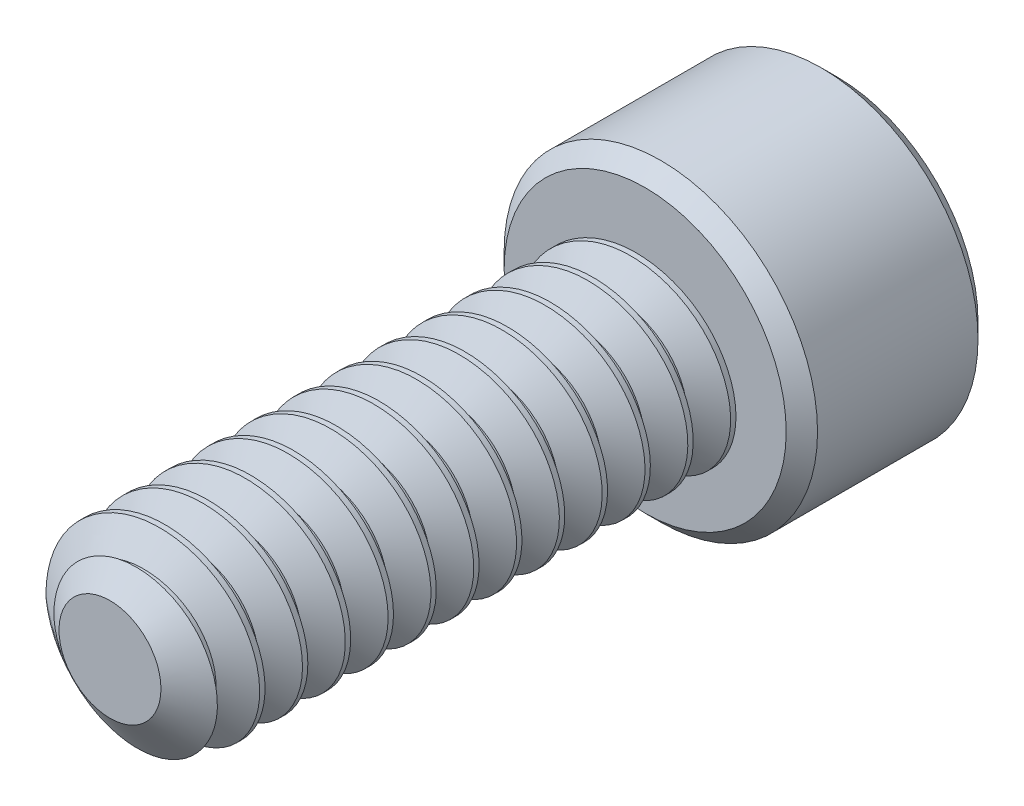
SolidWorks part; units mm, degrees
material "Alloy Steel"
ref_plane "Front Plane" through (0, 0, 0) normal (0, 0, 1) x (1, 0, 0)
ref_plane "Top Plane" through (0, 0, 0) normal (0, 1, 0) x (1, 0, 0)
ref_plane "Right Plane" through (0, 0, 0) normal (1, 0, 0) x (0, 0, -1)
sketch "Sketch1" plane through (0, 0, 0) normal (0, 0, 1) x (1, 0, 0)
  circle A0 centre (0, 0) radius 1.4224
  dimension "OD" = 2.8448
extrude "Extrude1" add sketch "Sketch1" against normal blind 7.9375
sketch "Sketch2" plane through (0, 0, 0) normal (0, 0, 1) x (1, 0, 0)
  circle A0 centre (0, 0) radius 1.4224 construction
  circle A1 centre (0, 0) radius 1.4224
curve "Helix/Spiral1" pitch 0.635 height 8.5725 turns 13.5 parameters "pitch"=0.635
sketch "Sketch3" plane through (0, 0, 0) normal (1, 0, 0) x (0, 0, -1)
  line L0 (-0.5556, 1.4224) -> (-0.3175, 1.01)
  line L1 (-0.3175, 1.01) -> (-0.2381, 1.01)
  line L2 (-0.2381, 1.01) -> (0, 1.4224)
  line L3 (-0.5556, 1.4224) -> (0, 1.4224)
  line L4 (-0.2778, 1.4224) -> (-0.2778, 1.01) construction
  line L5 (-0.4366, 1.2162) -> (-0.1191, 1.2162) construction
  line L6 (0, 1.4224) -> (0, -1.4224) construction
  dimension "D1" = 0.0794
  dimension "D2" = 0.3175
  dimension "D3" = 60
sweep "Cut-Sweep1" cut profiles "Sketch3" path "Helix/Spiral1"
sketch "Sketch4" plane through (0, 0, 0) normal (1, 0, 0) x (0, 0, -1)
  line L0 (0.4666, 1.4224) -> (0, 0.756)
  line L1 (0, 0.756) -> (0, 1.4224)
  line L2 (0.4666, 1.4224) -> (0, 1.4224)
  line L3 (-0.5556, 1.4224) -> (0, 1.4224) construction
  line L4 (0, 0) -> (7.0209, 0) construction
  dimension "D1" = 55
  dimension "D2" = 0.254
revolve "Cut-Revolve1" cut sketch "Sketch4" angle 360 about L4
sketch "Sketch5" plane through (0, 0, 0) normal (1, 0, 0) x (0, 0, -1)
  line L0 (7.9375, -1.0149) -> (7.9375, 1.0232) construction
  line L1 (7.9375, 1.5494) -> (38.1885, 1.5494)
  line L2 (7.9375, 1.5494) -> (7.9375, 0)
  line L3 (7.9375, 0) -> (38.1, 0)
  line L4 (38.1, 1.2192) -> (38.1, 0)
  line L5 (38.1885, 1.5494) -> (38.1, 1.2192)
  line L6 (0, 0) -> (9.9695, 0) construction
  point P3 (38.1, 1.5494)
  point P10 (38.1, 1.5494)
  dimension "D1" = 0.3302
  dimension "Thread min" = 38.1
  dimension "D2" = 0.127
  dimension "D3" = 15
revolve "partially thread" [suppressed] add sketch "Sketch5" angle 360 about L6
sketch "Sketch6" plane through (0, 0, -7.9375) normal (0, 0, -1) x (-1, 0, 0)
  circle A0 centre (0, 0) radius 2.3241
  dimension "head dia" = 4.6482
extrude "Extrude2" add sketch "Sketch6" along normal blind 2.8448
sketch "Sketch7" plane through (0, 0, -10.7823) normal (0, 0, -1) x (-1, 0, 0)
  line L1 (0, 1.3748) -> (-1.1906, 0.6874)
  line L2 (-1.1906, 0.6874) -> (-1.1906, -0.6874)
  line L3 (-1.1906, -0.6874) -> (0, -1.3748)
  line L4 (0, -1.3748) -> (1.1906, -0.6874)
  line L5 (1.1906, -0.6874) -> (1.1906, 0.6874)
  line L6 (1.1906, 0.6874) -> (0, 1.3748)
  circle A0 centre (0, 0) radius 1.1906 construction
  dimension "hex dia" = 2.3813
extrude "Cut-Extrude1" cut sketch "Sketch7" against normal blind 1.7859
sketch "Sketch8" plane through (0, 0, -10.7823) normal (0, 0, -1) x (-1, 0, 0)
  circle A0 centre (0, 0) radius 1.3748
extrude "Cut-Extrude2" cut sketch "Sketch8" against normal through all draft 45
chamfer "Chamfer1" distance 0.2324 angle 45 2 edges at (-2.3241, 0, -10.7823) (-2.3241, 0, -7.9375)
sketch "Sketch9" plane through (0, 0, 0) normal (1, 0, 0) x (0, 0, -1)
  line L0 (0, 1.4224) -> (0, -1.4224) construction
  line L1 (6.6675, 1.4224) -> (6.6675, -1.4224) construction
  dimension "D1" = 6.6675
equation "\"D3@Helix/Spiral1\" = \"screw length@Extrude1\"+\"pitch@Helix/Spiral1\""
equation "\"D1@Sketch3\" = \"pitch@Helix/Spiral1\"*.125"
equation "\"D2@Sketch3\" = \"pitch@Helix/Spiral1\"*.5"
equation "\"D1@Cut-Extrude1\" = \"hex dia@Sketch7\"*.75"
equation "\"D1@Chamfer1\" = \"head dia@Sketch6\"*.05"
equation "\"D1@Sketch9\" = \"pitch@Helix/Spiral1\"*10.5"
